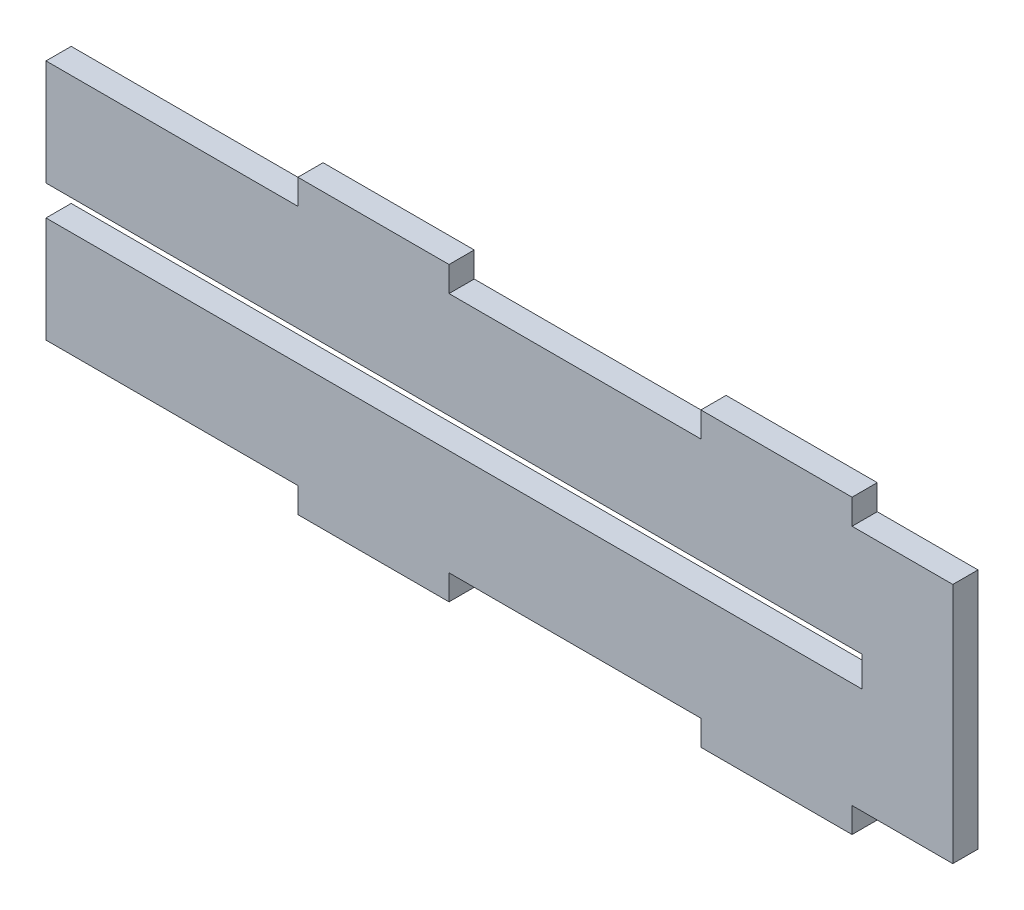
SolidWorks part; units mm, degrees
ref_plane "Plano frontal" through (0, 0, 0) normal (0, 0, 1) x (1, 0, 0)
ref_plane "Plano superior" through (0, 0, 0) normal (0, 1, 0) x (1, 0, 0)
ref_plane "Plano direito" through (0, 0, 0) normal (1, 0, 0) x (0, 0, -1)
sketch "Esboço1" plane through (0, 0, 0) normal (0, 0, 1) x (1, 0, 0)
  line L0 (0, -48) -> (50, -48)
  line L1 (0, 0) -> (50, 0)
  line L2 (0, 0) -> (0, -48)
  line L3 (50, -53) -> (80, -53)
  line L5 (50, -48) -> (50, -53)
  line L6 (80, -53) -> (80, -48)
  line L7 (80, -48) -> (130, -48)
  line L8 (130, -48) -> (130, -53)
  line L9 (160, -53) -> (160, -48)
  line L10 (160, -48) -> (180, -48)
  line L11 (130, -53) -> (160, -53)
  line L12 (0, -24) -> (180, -24) construction
  line L13 (0, 0) -> (50, 0)
  line L14 (80, 0) -> (130, 0)
  line L15 (160, 0) -> (180, 0)
  line L16 (160, 5) -> (160, 0)
  line L17 (130, 5) -> (160, 5)
  line L18 (130, 0) -> (130, 5)
  line L19 (80, 5) -> (80, 0)
  line L20 (50, 5) -> (80, 5)
  line L21 (50, 0) -> (50, 5)
  line L22 (80, 0) -> (130, 0)
  line L23 (160, 0) -> (180, 0)
  line L24 (180, 0) -> (180, -48)
  line L25 (0, -21) -> (162, -21)
  line L26 (0, -21) -> (0, -27)
  line L27 (0, -27) -> (162, -27)
  line L28 (162, -21) -> (162, -27)
  point P27 (0, -24)
  dimension "D2" = 48
  dimension "D3" = 50
  dimension "D4" = 5
  dimension "D5" = 30
  dimension "D6" = 50
  dimension "D7" = 5
  dimension "D8" = 30
  dimension "D9" = 5
  dimension "D10" = 180
  dimension "D11" = 162
  dimension "D12" = 6
  dimension "D14" = 30
extrude "Ressalto-extrusão1" add sketch "Esboço1" along normal blind 5 contours L12 L2 L0 L5 L3 L6 L7 L8 L11 L9 L10 | L2 L12 L15 L16 L17 L18 L14 L19 L20 L21 L1 region at (1.8911, -37.5, 0)
